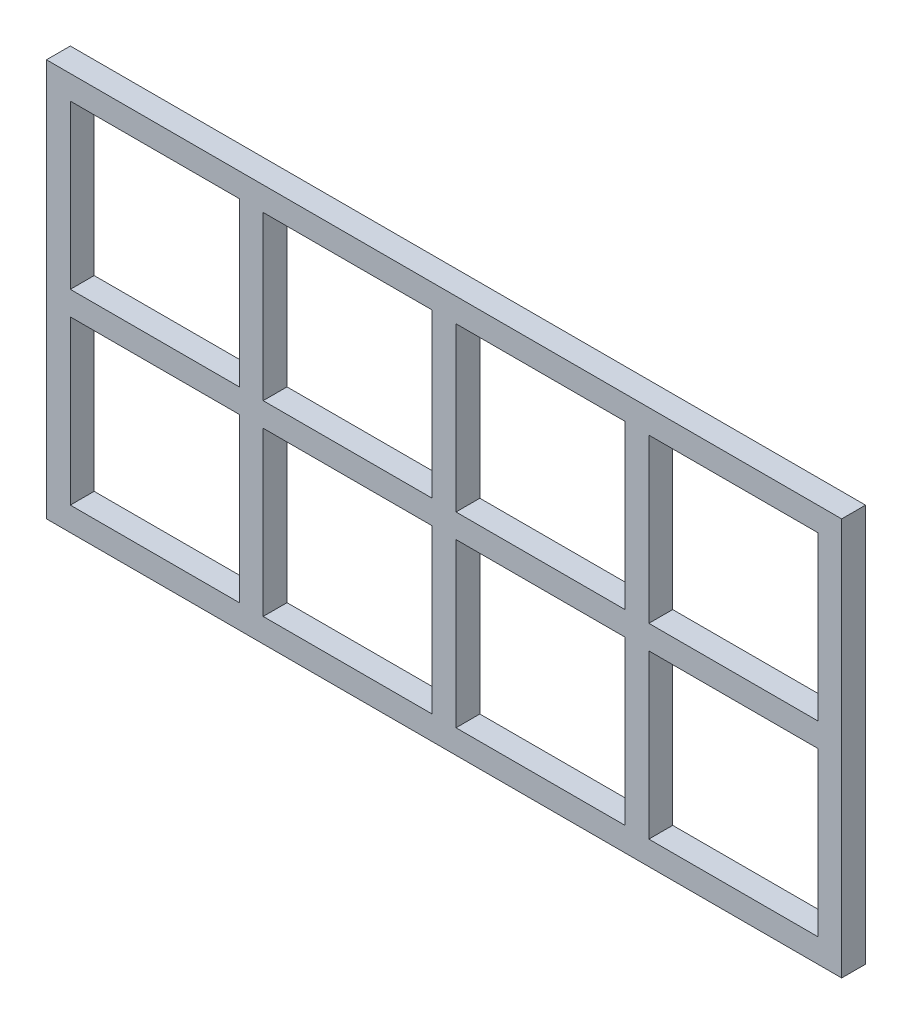
SolidWorks part; units mm, degrees
ref_plane "Front Plane" through (0, 0, 0) normal (0, 0, 1) x (1, 0, 0)
ref_plane "Top Plane" through (0, 0, 0) normal (0, 1, 0) x (1, 0, 0)
ref_plane "Right Plane" through (0, 0, 0) normal (1, 0, 0) x (0, 0, -1)
sketch "Sketch1" plane through (0, 0, 0) normal (0, 0, 1) x (1, 0, 0)
  line L1 (-637.4914, 238.1325) -> (362.5086, 238.1325)
  line L2 (-637.4914, 238.1325) -> (-637.4914, -261.8675)
  line L3 (-637.4914, -261.8675) -> (362.5086, -261.8675)
  line L4 (362.5086, 238.1325) -> (362.5086, -261.8675)
  line L11 (-244.284, -261.8675) -> (-199.2608, -261.8675)
  line L28 (362.5086, -202.3601) -> (362.5086, -252.3601)
  line L43 (-607.4914, -26.8675) -> (-607.4914, -231.8675)
  line L44 (-364.9914, 208.1325) -> (-152.4914, 208.1325)
  line L45 (-607.4914, 208.1325) -> (-394.9914, 208.1325)
  line L46 (-607.4914, 208.1325) -> (-607.4914, 3.1325)
  line L47 (-607.4914, -231.8675) -> (-394.9914, -231.8675)
  line L48 (332.5086, 208.1325) -> (332.5086, 3.1325)
  line L52 (-364.9914, 208.1325) -> (-364.9914, 3.1325)
  line L54 (-394.9914, 208.1325) -> (-394.9914, 3.1325)
  line L57 (-364.9914, -231.8675) -> (-152.4914, -231.8675)
  line L58 (120.0086, 208.1325) -> (120.0086, 3.1325)
  line L59 (90.0086, 208.1325) -> (90.0086, 3.1325)
  line L60 (120.0086, 208.1325) -> (332.5086, 208.1325)
  line L61 (120.0086, -231.8675) -> (332.5086, -231.8675)
  line L62 (-122.4914, 208.1325) -> (90.0086, 208.1325)
  line L64 (-122.4914, 208.1325) -> (-122.4914, 3.1325)
  line L66 (-152.4914, 208.1325) -> (-152.4914, 3.1325)
  line L72 (-622.6592, 238.1325) -> (-622.6592, 428.8419) construction
  line L76 (-122.4914, -231.8675) -> (90.0086, -231.8675)
  line L79 (-607.4914, -26.8675) -> (-394.9914, -26.8675)
  line L81 (-637.6592, 119.4956) -> (-637.6592, 89.4956)
  line L83 (362.5086, 19.4956) -> (362.5086, -10.5044)
  line L84 (-394.9914, -26.8675) -> (-394.9914, -231.8675)
  line L87 (-364.9914, 3.1325) -> (-152.4914, 3.1325)
  line L89 (-607.4914, 3.1325) -> (-394.9914, 3.1325)
  line L90 (-364.9914, -26.8675) -> (-152.4914, -26.8675)
  line L92 (-364.9914, -26.8675) -> (-364.9914, -231.8675)
  line L102 (-122.4914, -26.8675) -> (90.0086, -26.8675)
  line L103 (-122.4914, 3.1325) -> (90.0086, 3.1325)
  line L104 (-152.4914, -26.8675) -> (-152.4914, -231.8675)
  line L105 (-122.4914, -26.8675) -> (-122.4914, -231.8675)
  line L107 (120.0086, 3.1325) -> (332.5086, 3.1325)
  line L108 (120.0086, -26.8675) -> (332.5086, -26.8675)
  line L110 (90.0086, -26.8675) -> (90.0086, -231.8675)
  line L111 (120.0086, -26.8675) -> (120.0086, -231.8675)
  line L112 (332.5086, -26.8675) -> (332.5086, -231.8675)
  point P0 (0, 0)
  point P6 (0, 0)
  point P8 (0, 0)
  point P9 (0, 0)
  point P10 (-137.6592, 104.4956)
  point P11 (-225, 0)
  point P16 (0, 0)
  point P18 (0, 0)
  point P21 (-372.6592, 77.1356)
  point P30 (-137.6592, 89.4956)
  point P46 (-137.6592, 104.4956)
  dimension "D1" = 1000
  dimension "D2" = 500
  dimension "D3" = 212.5
  dimension "D4" = 30
  dimension "D5" = 30
  dimension "D6" = 30
  dimension "D7" = 30
  dimension "D8" = 30
  dimension "D9" = 30
  dimension "D10" = 30
  dimension "D11" = 205
  dimension "D12" = 30
  dimension "D13" = 30
  dimension "D14" = 212.5
  dimension "D15" = 212.5
  dimension "D16" = 30
  dimension "D17" = 212.5
extrude "Boss-Extrude1" add sketch "Sketch1" along normal blind 30 contours L4 L1 L2 L3 L54 L47 region at (-137.4914, -11.8675, 0)
